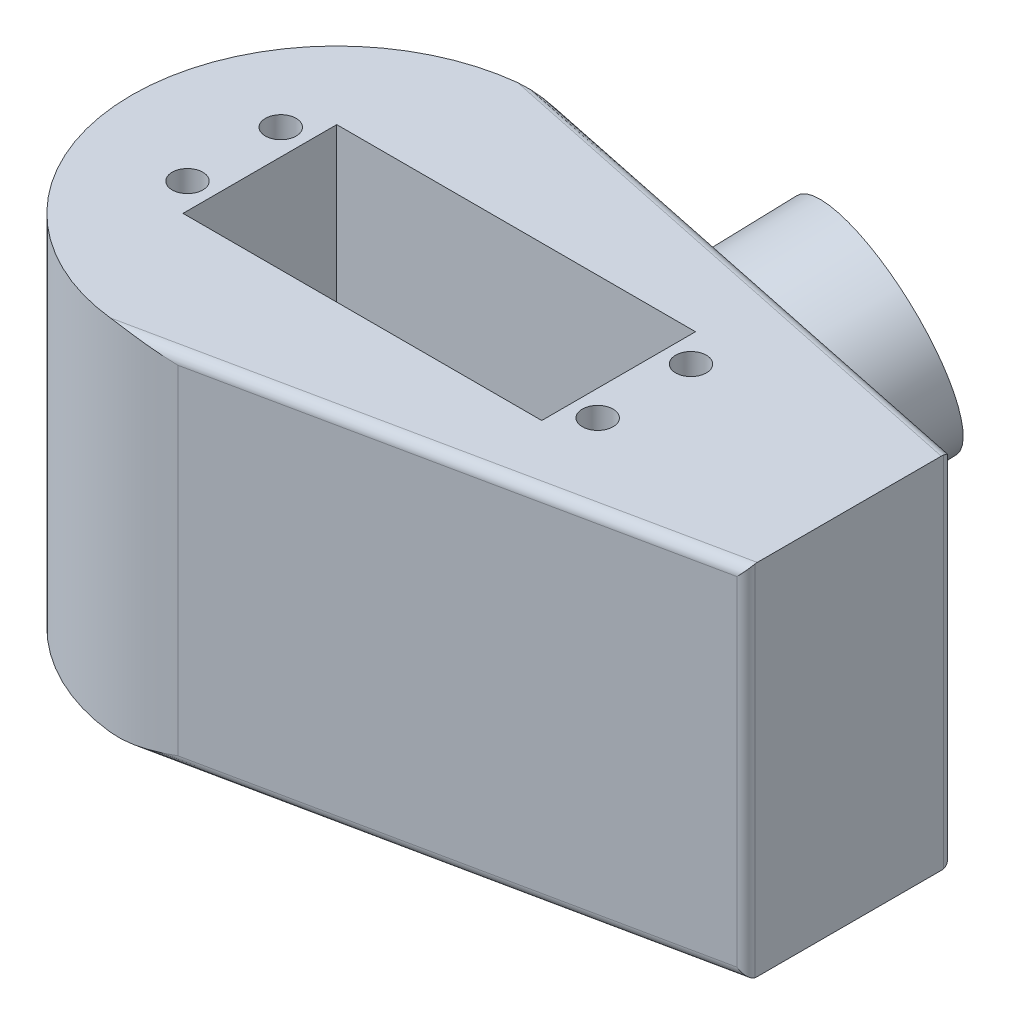
SolidWorks part; units mm, degrees
note: The reader was unsure of these and kept them because the rebuilt part matched: shared geometry of "Sketch3<3>".
material "ABS"
ref_plane "Front Plane" through (0, 0, 0) normal (0, 0, 1) x (1, 0, 0)
ref_plane "Top Plane" through (0, 0, 0) normal (0, 1, 0) x (1, 0, 0)
ref_plane "Right Plane" through (0, 0, 0) normal (1, 0, 0) x (0, 0, -1)
sketch "Sketch1" plane through (0, 0, 0) normal (0, 1, 0) x (1, 0, 0)
  line L0 (0, 0) -> (50, 0) construction
  line L1 (50, 10) -> (50, -10)
  line L2 (4.0843, 19.5785) -> (50, 10)
  line L3 (50, -10) -> (4.0843, -19.5785)
  arc A0 (4.0843, 19.5785) -> (4.0843, -19.5785) centre (0, 0) ccw
  point P3 (50, 0)
  dimension "D1" = 20
  dimension "D2" = 50
  dimension "D3" = 20
extrude "Boss-Extrude1" add sketch "Sketch1" along normal blind 35
sketch "Sketch2" plane through (0, 35, 0) normal (0, 1, 0) x (1, 0, 0)
  line L0 (0, 0) -> (-7.5, 0) construction
  line L1 (-7.5, 7.5) -> (27.5, 7.5)
  line L2 (-7.5, 7.5) -> (-7.5, -7.5)
  line L3 (-7.5, -7.5) -> (27.5, -7.5)
  line L4 (27.5, 7.5) -> (27.5, -7.5)
  dimension "D1" = 15
  dimension "D2" = 35
  dimension "D3" = 7.5
extrude "Cut-Extrude1" cut sketch "Sketch2" against normal blind 15
fillet "Fillet1" radius 1 6 edges at (50, 17.5, -10) (27.0421, 35, -14.7893) (27.0421, 0, -14.7893) (27.0421, 35, 14.7893) (50, 17.5, 10) (27.0421, 0, 14.7893)
sketch "Sketch3" plane through (0, 0, 0) normal (0, -1, 0) x (1, 0, 0)
  circle A0 centre (0, 0) radius 7.5
  circle A1 centre (0, 0) radius 3
  dimension "D1" = 15
  dimension "D2" = 6
extrude "Cut-Extrude2" cut sketch "Sketch3" against normal blind 10 contours A1 | A0 A1
extrude "Cut-Extrude3" cut sketch "Sketch3<3>" against normal through all contours A1
sketch "Sketch3<3>" plane through (0, 0, 0) normal (0, -1, 0) x (1, 0, 0) same geometry as "Sketch3"
ref_plane "Plane1" through (0, 4.431, 15.9775) normal (0, 0.2672, 0.9636) x (1, 0, 0)
sketch "Sketch4" plane through (0, 4.431, 15.9775) normal (0, 0.2672, 0.9636) x (1, 0, 0)
  line L0 (17, 0) -> (17, 25) construction
  dimension "D1" = 17
  dimension "D2" = 25
ref_plane "Plane2" through (4.5101, 5.204, 18.765) normal (0.2256, 0.2603, 0.9388) x (0, 0.9636, -0.2672)
sketch "Sketch5" plane through (4.5101, 5.204, 18.765) normal (0.2256, 0.2603, 0.9388) x (0, 0.9636, -0.2672)
  circle A0 centre (10.36, -11.75) radius 10
  dimension "D1" = 20
  dimension "D2" = 11.75
  dimension "D3" = 10.36
extrude "Extrude-Thin1" add sketch "Sketch5" along normal blind 20 thin
sketch "Sketch6" plane through (0, 35, 0) normal (0, 1, 0) x (1, 0, 0)
  line L0 (-7.5, 7.5) -> (-7.5, -7.5) construction
  line L1 (27.5, 7.5) -> (-7.5, 7.5) construction
  line L2 (10, 7.5) -> (10, -7.5) construction
  line L3 (-7.5, -7.5) -> (27.5, -7.5) construction
  line L4 (-19.8375, 0) -> (19.8375, 0) construction
  circle A0 centre (-10.01, 4.55) radius 1.5
  circle A1 centre (-10.01, -4.55) radius 1.5
  circle A2 centre (30.01, -4.55) radius 1.5
  circle A3 centre (30.01, 4.55) radius 1.5
  dimension "D1" = 3
  dimension "D2" = 2.51
  dimension "D3" = 2.95
extrude "Cut-Extrude4" cut sketch "Sketch6" against normal blind 8.2
ref_plane "Plane3" through (0, 0, -27.5) normal (0, 0, 1) x (1, 0, 0)
mirror "Mirror1" about plane through (0, 0, -27.5) normal (0, 0, 1) of bodies 108 106
delete or keep bodies "Body-Delete/Keep 1" type delete bodies bodies 108
